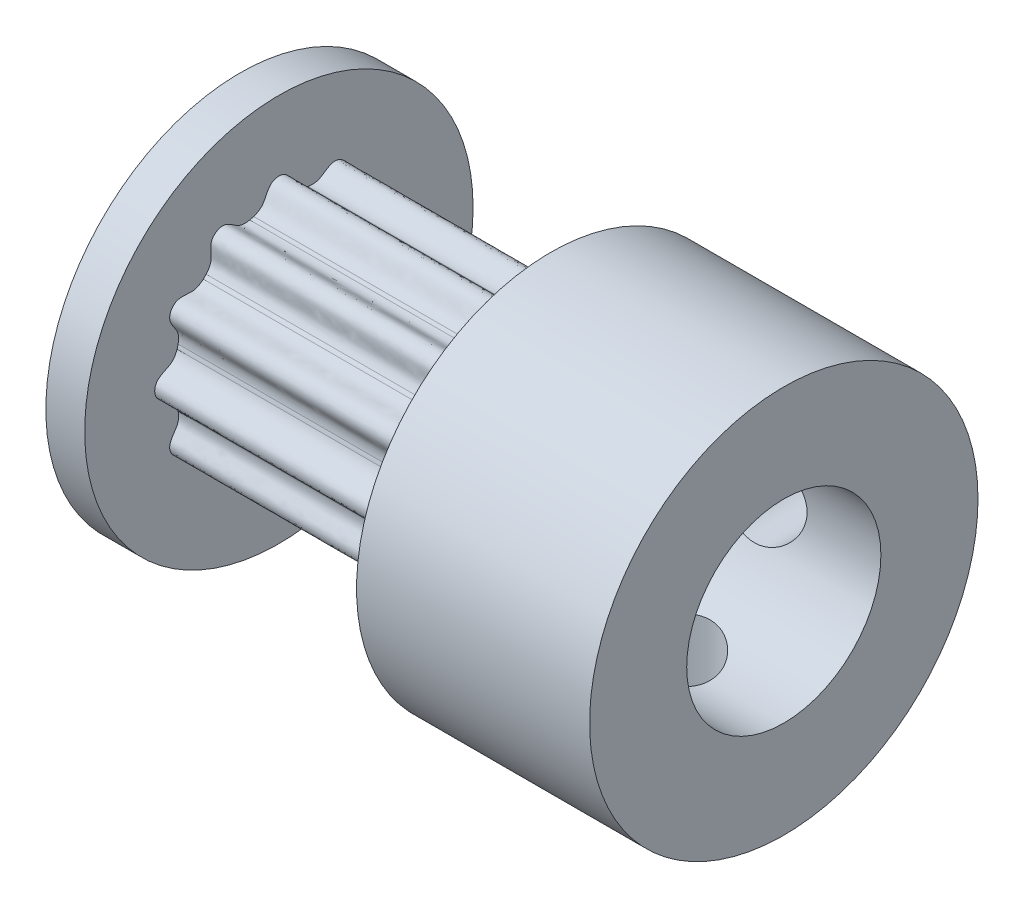
SolidWorks part; units mm, degrees
material "6063-T5"
ref_plane "Спереди" through (0, 0, 0) normal (0, 0, 1) x (1, 0, 0)
ref_plane "Сверху" through (0, 0, 0) normal (0, 1, 0) x (1, 0, 0)
ref_plane "Справа" through (0, 0, 0) normal (1, 0, 0) x (0, 0, -1)
sketch "Sketch1" plane through (0, 0, 0) normal (0, 1, 0) x (1, 0, 0)
  line L0 (0, 0) -> (-14, 0) construction
  line L1 (0, 2.5) -> (-14, 2.5)
  line L2 (-14, 2.5) -> (-14, 5)
  line L3 (-14, 5) -> (-13, 5)
  line L4 (-13, 5) -> (-13, 2.7)
  line L5 (-13, 2.7) -> (-6, 2.7)
  line L6 (-6, 2.7) -> (-6, 5)
  line L7 (-6, 5) -> (0, 5)
  line L8 (0, 5) -> (0, 2.5)
  dimension "D1" = 14
  dimension "D2" = 10
  dimension "D3" = 5
  dimension "D4" = 1
  dimension "D5" = 5.4
  dimension "D6" = 6
revolve "Base" add sketch "Sketch1" angle 360 about L0
sketch "Sketch2" plane through (-14, 0, 0) normal (-1, 0, 0) x (0, 0, 1)
  line L0 (0, 0) -> (0, 5.8) construction
  line L1 (0, 0) -> (-1.5541, 5.8) construction
  line L2 (0, 0) -> (1.5541, 5.8) construction
  line L6 (0, 0) -> (-0.7636, 5.8) construction
  circle A0 centre (0, 0) radius 3.2 construction
  arc A1 (-0.698, 2.605) -> (0.698, 2.605) centre (0, 0.088) cw
  circle A14 centre (0, 0) radius 2.7 construction
  spline S0 degree 3 poles (-0.698, 2.605) (-0.5791, 2.6401) (-0.4329, 2.7095) (-0.2648, 3.077) (-0.1835, 3.1877) (0, 3.2) knots 0 0 0 0 0.181357 0.234422 0.530653 0.530653 0.530653 0.530653 construction
  spline S1 degree 3 poles (0.698, 2.605) (0.5791, 2.6401) (0.4329, 2.7095) (0.2648, 3.077) (0.1835, 3.1877) (0, 3.2) knots 0 0 0 0 0.181357 0.234422 0.530653 0.530653 0.530653 0.530653 construction
  spline S2 degree 3 poles (-0.698, 2.605) (-0.5791, 2.6401) (-0.4329, 2.7095) (-0.2933, 3.0148) (-0.2272, 3.1221) (-0.1391, 3.166) (-0.1114, 3.1798) (-0.0514, 3.1979) (0.0514, 3.1979) (0.1114, 3.1798) (0.1391, 3.166) (0.2272, 3.1221) (0.2933, 3.0148) (0.4329, 2.7095) (0.5791, 2.6401) (0.698, 2.605) knots 0 0 0 0 0.168536 0.217849 0.409697 0.409697 0.409697 0.469899 0.530101 0.590303 0.590303 0.590303 0.782151 0.831464 1 1 1 1
  point P72 (0, 0)
  point P98 (0, 0)
  dimension "D1" = 6.4
  dimension "D6" = 12
  dimension "D7" = 5.4
  dimension "D2" = 30
  dimension "D3" = 5.8
  dimension "D4" = 15
  dimension "D5" = 7.5
extrude "Tooth" add sketch "Sketch2" against normal blind 9 contours S0 | S2 A1 region at (-14, 2.8888, 0)
pattern_circular "Teeth" count 12 over 360 about axis through (0, 0, 0) along (1, 0, 0) of "Tooth"
sketch "Sketch3" plane through (0, 0, 0) normal (0, 0, 1) x (1, 0, 0)
  line L0 (0, -5) -> (0, 5) construction
  circle A0 centre (-3, 0) radius 1.1
  dimension "D1" = 2.2
  dimension "D2" = 3
extrude "SetScrewHole1" cut sketch "Sketch3" against normal blind 6
cosmetic thread "Cosmetic Thread1" parameters "D2"=3
sketch "Sketch4" plane through (0, 0, 0) normal (0, 1, 0) x (1, 0, 0)
  line L0 (0, -5) -> (0, 5) construction
  circle A0 centre (-3, 0) radius 1.1
  dimension "D1" = 3
  dimension "D2" = 2.2
extrude "SetScrewHole2" cut sketch "Sketch4" against normal blind 6
cosmetic thread "Cosmetic Thread2" parameters "D2"=3
